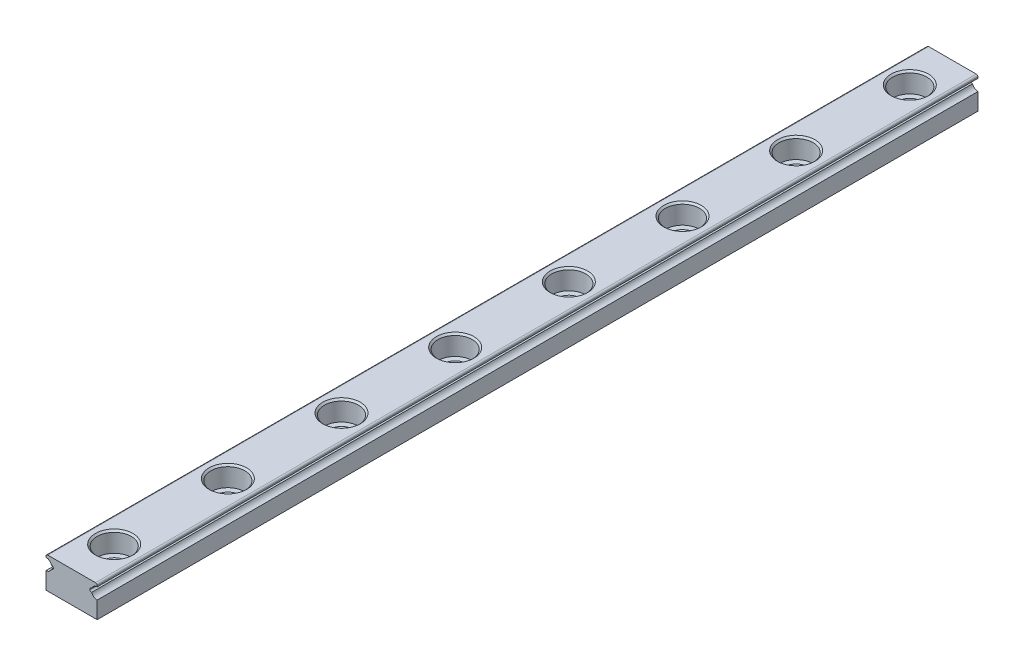
SolidWorks part; units mm, degrees
ref_plane "Front Plane" through (0, 0, 0) normal (0, 0, 1) x (1, 0, 0)
ref_plane "Top Plane" through (0, 0, 0) normal (0, 1, 0) x (1, 0, 0)
ref_plane "Right Plane" through (0, 0, 0) normal (1, 0, 0) x (0, 0, -1)
sketch "Sketch1" plane through (0, 0, 0) normal (0, 0, 1) x (1, 0, 0)
  line L0 (-4.5, 2.75) -> (-4.5, 1.25)
  line L1 (-4.5, -2.75) -> (4.5, -2.75)
  line L2 (-4.5, -2.75) -> (-4.5, 2.75)
  line L3 (-4.5, 2.75) -> (4.5, 2.75)
  line L4 (4.5, -2.75) -> (4.5, 2.75)
  line L5 (-4.5, -2.75) -> (4.5, 2.75) construction
  line L6 (-4.5, 2.75) -> (4.5, -2.75) construction
  line L7 (0, 0) -> (0, 6.0427) construction
  line L8 (-4.5, 1.25) -> (8.8356, 1.25) construction
  circle A0 centre (-4.5, 1.25) radius 1
  circle A1 centre (4.5, 1.25) radius 1
  circle A2 centre (-3.5, 1.25) radius 0.3
  circle A3 centre (3.5, 1.25) radius 0.3
  point P0 (0, 0)
  dimension "D4" = 2
  dimension "D5" = 0.6
  dimension "D1" = 5.5
  dimension "D2" = 9
  dimension "D3" = 1.5
extrude "Boss-Extrude1" add sketch "Sketch1" along normal blind 155 contours A1 A3 L4 L3 L0 A0 A2 L2 L1 region at (0, -0.0934, 0)
fillet "Fillet1" radius 0.3 2 edges at (4.5, 2.75, 77.5) (-4.5, 2.75, 77.5)
sketch "Sketch2" plane through (0, 2.75, 0) normal (0, 1, 0) x (1, 0, 0)
  line L0 (0, 0) -> (0, -7.5)
  line L1 (-4.2, 0) -> (4.2, 0) construction
  circle A0 centre (0, -7.5) radius 1.75
  circle A1 centre (0, -7.5) radius 3
  dimension "D2" = 3.5
  dimension "D3" = 6
  dimension "D1" = 7.5
extrude "Cut-Extrude1" cut sketch "Sketch2" against normal blind 155 contours A0 region at (1.2024, 2.75, 6.2976)
extrude "Cut-Extrude2" cut sketch "Sketch2<3>" against normal blind 3.5 contours A1 A0 region at (2.0613, 2.75, 5.4387)
sketch "Sketch2<3>" plane through (0, 2.75, 0) normal (0, 1, 0) x (1, 0, 0) same geometry as "Sketch2"
chamfer "Chamfer1" distance 0.3 angle 45 2 edges at (-1.75, -0.75, 7.5) (-3, 2.75, 7.5)
pattern_linear "LPattern1" count 8 spacing 20 along (0, 0, 1) of "Chamfer1", "Cut-Extrude2", "Cut-Extrude1"
